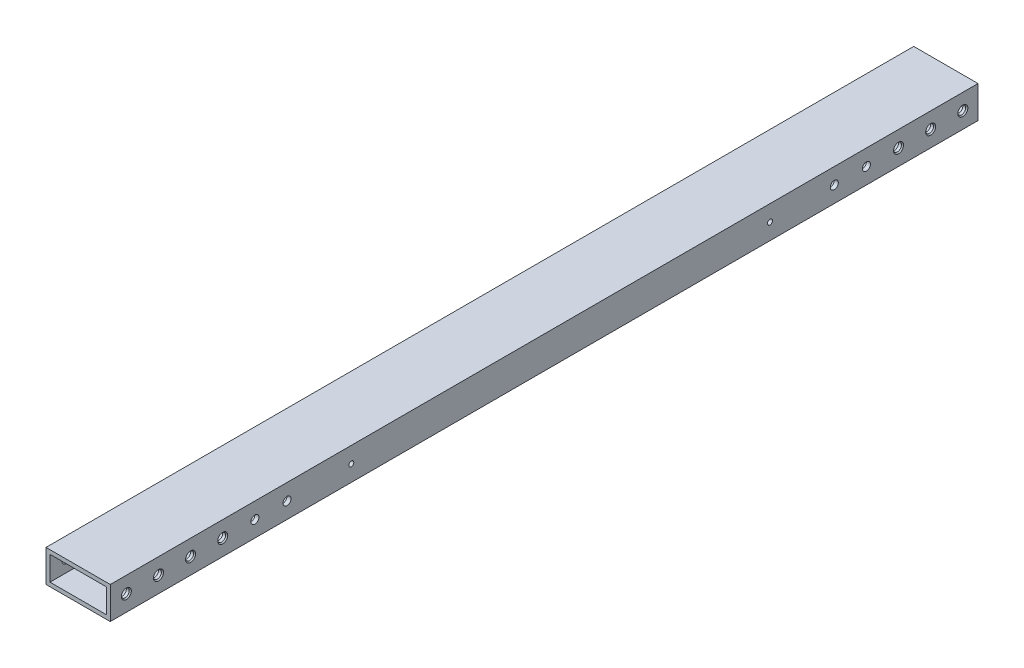
SolidWorks part; units mm, degrees
material "6061 Alloy"
ref_plane "Front Plane" through (0, 0, 0) normal (0, 0, 1) x (1, 0, 0)
ref_plane "Top Plane" through (0, 0, 0) normal (0, 1, 0) x (1, 0, 0)
ref_plane "Right Plane" through (0, 0, 0) normal (1, 0, 0) x (0, 0, -1)
sketch "Sketch1" plane through (0, 0, 0) normal (0, 0, 1) x (1, 0, 0)
  line L0 (-22.225, 9.525) -> (22.225, 9.525)
  line L2 (-25.4, 12.7) -> (25.4, 12.7)
  line L3 (-25.4, 12.7) -> (-25.4, -12.7)
  line L4 (-25.4, -12.7) -> (25.4, -12.7)
  line L5 (25.4, 12.7) -> (25.4, -12.7)
  line L10 (22.225, 9.525) -> (22.225, -9.525)
  line L11 (-22.225, -9.525) -> (22.225, -9.525)
  line L12 (-22.225, 9.525) -> (-22.225, -9.525)
  point P12 (0, 12.7)
  point P14 (25.4, 0)
  dimension "Wall Thickness" = 3.175
  dimension "Outside Width" = 50.8
  dimension "Outside Height" = 25.4
  dimension "Inside Height" = 19.05
  dimension "Inside Width" = 44.45
sketch "Sketch2" plane through (0, 0, 0) normal (1, 0, 0) x (0, 0, -1)
  line L0 (342.9, 0) -> (-342.9, 0)
  point P4 (0, 0)
  point P7 (-342.9, 0)
  point P10 (342.9, 0)
  dimension "Length" = 685.8
sketch "Sketch3" plane through (0, 0, 0) normal (0, 0, 1) x (1, 0, 0)
  line L21 (25.4, 12.7) -> (-25.4, 12.7)
  line L22 (25.4, -12.7) -> (25.4, 12.7)
  line L23 (-25.4, -12.7) -> (25.4, -12.7)
  line L24 (-25.4, 12.7) -> (-25.4, -12.7)
  line L25 (25.4, 12.7) -> (-25.4, 12.7)
  line L26 (25.4, -12.7) -> (25.4, 12.7)
  line L27 (-25.4, -12.7) -> (25.4, -12.7)
  line L28 (-25.4, 12.7) -> (-25.4, -12.7)
  line L29 (22.225, 9.525) -> (-22.225, 9.525)
  line L30 (22.225, -9.525) -> (22.225, 9.525)
  line L31 (-22.225, -9.525) -> (22.225, -9.525)
  line L32 (-22.225, 9.525) -> (-22.225, -9.525)
  line L33 (22.225, 9.525) -> (-22.225, 9.525)
  line L34 (22.225, -9.525) -> (22.225, 9.525)
  line L35 (-22.225, -9.525) -> (22.225, -9.525)
  line L36 (-22.225, 9.525) -> (-22.225, -9.525)
  dimension "D1" = 0
  dimension "D2" = 0
extrude "Boss-Extrude1" add sketch "Sketch3" along normal up to vertex (342.9 mm away) and the other way up to vertex (342.9 mm away) up to point (0, 0, 342.9) other way up to point (0, 0, -342.9)
sketch "Drawing Reference" plane through (0, 0, 0) normal (1, 0, 0) x (0, 0, -1)
  line L0 (-342.9, 0) -> (342.9, 0) construction
  line L1 (0, -12.7) -> (0, 12.7) construction
  line L2 (-342.9, -12.7) -> (342.9, -12.7) construction
  line L5 (-342.9, 12.7) -> (342.9, 12.7) construction
  point P7 (-306.324, 0)
  point P8 (306.324, 0)
  dimension "D1" = 36.576
sketch "Sketch5" plane through (25.4, 0, 0) normal (1, 0, 0) x (0, 0, -1)
  line L0 (-342.9, 0) -> (-279.4, 0)
  line L1 (-342.9, -12.7) -> (-342.9, 12.7) construction
  line L2 (-279.4, 0) -> (-254, 0)
  line L3 (-254, 0) -> (-228.6, 0)
  line L4 (-228.6, 0) -> (-203.2, 0)
sketch "Sketch8" plane through (25.4, 0, 0) normal (1, 0, 0) x (0, 0, -1)
  line L0 (342.9, 0) -> (305.5118, 0)
  line L1 (342.9, -12.7) -> (342.9, 12.7) construction
  line L2 (305.5118, 0) -> (280.1118, 0)
  line L3 (280.1118, 0) -> (254.7118, 0)
  line L4 (254.7118, 0) -> (229.3118, 0)
hole_wizard "1/4 (0.25) Diameter Hole3" positions "Sketch12" profile "Sketch13" hole size "1/4" standard "ANSI Inch" end condition through all
sketch "Sketch12" plane through (-25.4, 0, 0) normal (-1, 0, 0) x (0, 0, 1)
  point P0 (-330.9118, 0)
sketch "Sketch13" plane through (-25.4, 0, -330.9118) normal (0, 1, 0) x (0, 0, 1)
  line L0 (0, 0) -> (0, 50.8)
  line L1 (0, 50.8) -> (3.9624, 50.8)
  line L2 (3.175, 49.8942) -> (3.175, 0)
  line L5 (3.175, 0) -> (0, 0)
  line L7 (3.9624, 50.8) -> (3.175, 49.8942)
  line L8 (-3.9624, 50.8) -> (-3.175, 49.8942) construction
  line L11 (0, -6.35) -> (0, 107.95) construction
  dimension "Thru Hole Dia." = 6.35
  dimension "Thru Hole Depth" = 50.8
  dimension "Far C'Sink Dia." = 7.9248
  dimension "Far C'Sink Angle" = 82
hole_wizard "1/4 (0.25) Diameter Hole4" positions "Sketch14" profile "Sketch15" hole size "1/4" standard "ANSI Inch" end condition through all
sketch "Sketch14" plane through (-25.4, 0, 0) normal (-1, 0, 0) x (0, 0, 1)
  point P0 (304.8, 0)
  point P3 (330.2, 0)
sketch "Sketch15" plane through (-25.4, 0, 304.8) normal (0, 1, 0) x (0, 0, 1)
  line L0 (0, 0) -> (0, 50.8)
  line L1 (0, 50.8) -> (3.9624, 50.8)
  line L2 (3.175, 49.8942) -> (3.175, 0)
  line L5 (3.175, 0) -> (0, 0)
  line L7 (3.9624, 50.8) -> (3.175, 49.8942)
  line L8 (-3.9624, 50.8) -> (-3.175, 49.8942) construction
  line L11 (0, -6.35) -> (0, 107.95) construction
  dimension "Thru Hole Dia." = 6.35
  dimension "Thru Hole Depth" = 50.8
  dimension "Far C'Sink Dia." = 7.9248
  dimension "Far C'Sink Angle" = 82
hole_wizard "1/4 (0.25) Diameter Hole5" positions "Sketch17" profile "Sketch18" hole size "1/4" standard "ANSI Inch" end condition through all
sketch "Sketch17" plane through (25.4, 0, 0) normal (1, 0, 0) x (0, 0, -1)
  point P0 (305.5118, 0)
  point P3 (280.1118, 0)
sketch "Sketch18" plane through (25.4, 0, -305.5118) normal (0, 1, 0) x (0, 0, -1)
  line L0 (0, 0) -> (0, 50.8)
  line L1 (0, 50.8) -> (3.175, 50.8)
  line L2 (3.175, 50.8) -> (3.175, 0.9058)
  line L3 (3.175, 0.9058) -> (3.9624, 0)
  line L5 (3.9624, 0) -> (0, 0)
  line L6 (-3.175, 0.9058) -> (-3.9624, 0) construction
  line L11 (0, -6.35) -> (0, 107.95) construction
  dimension "Thru Hole Dia." = 6.35
  dimension "Thru Hole Depth" = 50.8
  dimension "Near C'Sink Dia." = 7.9248
  dimension "Near C'Sink Angle" = 82
hole_wizard "1/4 (0.25) Diameter Hole6" positions "Sketch19" profile "Sketch20" hole size "1/4" standard "ANSI Inch" end condition through all
sketch "Sketch19" plane through (25.4, 0, 0) normal (1, 0, 0) x (0, 0, -1)
  point P0 (229.3118, 0)
  point P3 (254.7118, 0)
sketch "Sketch20" plane through (25.4, 0, -229.3118) normal (0, 1, 0) x (0, 0, -1)
  line L0 (0, 0) -> (0, 50.8)
  line L1 (0, 50.8) -> (3.175, 50.8)
  line L2 (3.175, 50.8) -> (3.175, 0)
  line L5 (3.175, 0) -> (0, 0)
  line L11 (0, -6.35) -> (0, 107.95) construction
  dimension "Thru Hole Dia." = 6.35
  dimension "Thru Hole Depth" = 50.8
hole_wizard "1/4 (0.25) Diameter Hole7" positions "Sketch21" profile "Sketch22" hole size "1/4" standard "ANSI Inch" end condition through all
sketch "Sketch21" plane through (25.4, 0, 0) normal (1, 0, 0) x (0, 0, -1)
  point P0 (-203.2, 0)
  point P3 (-228.6, 0)
sketch "Sketch22" plane through (25.4, 0, 203.2) normal (0, 1, 0) x (0, 0, -1)
  line L0 (0, 0) -> (0, 50.8)
  line L1 (0, 50.8) -> (3.175, 50.8)
  line L2 (3.175, 50.8) -> (3.175, 0)
  line L5 (3.175, 0) -> (0, 0)
  line L11 (0, -6.35) -> (0, 107.95) construction
  dimension "Thru Hole Dia." = 6.35
  dimension "Thru Hole Depth" = 50.8
hole_wizard "1/4 (0.25) Diameter Hole8" positions "Sketch23" profile "Sketch24" hole size "1/4" standard "ANSI Inch" end condition through all
sketch "Sketch23" plane through (25.4, 0, 0) normal (1, 0, 0) x (0, 0, -1)
  point P0 (-279.4, 0)
  point P3 (-254, 0)
sketch "Sketch24" plane through (25.4, 0, 279.4) normal (0, 1, 0) x (0, 0, -1)
  line L0 (0, 0) -> (0, 50.8)
  line L1 (0, 50.8) -> (3.175, 50.8)
  line L2 (3.175, 50.8) -> (3.175, 0.9058)
  line L3 (3.175, 0.9058) -> (3.9624, 0)
  line L5 (3.9624, 0) -> (0, 0)
  line L6 (-3.175, 0.9058) -> (-3.9624, 0) construction
  line L11 (0, -6.35) -> (0, 107.95) construction
  dimension "Thru Hole Dia." = 6.35
  dimension "Thru Hole Depth" = 50.8
  dimension "Near C'Sink Dia." = 7.9248
  dimension "Near C'Sink Angle" = 82
sketch "Sketch25" plane through (25.4, 0, 0) normal (1, 0, 0) x (0, 0, -1)
  line L0 (-203.2, 0) -> (-152.4, 0)
  line L1 (229.3118, 0) -> (178.5118, 0)
hole_wizard "5/32 (0.15625) Diameter Hole1" positions "Sketch26" profile "Sketch27" hole size "5/32" standard "ANSI Inch" end condition through all
sketch "Sketch26" plane through (25.4, 0, 0) normal (1, 0, 0) x (0, 0, -1)
  point P0 (-152.4, 0)
  point P3 (178.5118, 0)
sketch "Sketch27" plane through (25.4, 0, 152.4) normal (0, 1, 0) x (0, 0, -1)
  line L0 (0, 0) -> (0, 50.8)
  line L1 (0, 50.8) -> (1.9844, 50.8)
  line L2 (1.9844, 50.8) -> (1.9844, 0)
  line L5 (1.9844, 0) -> (0, 0)
  line L11 (0, -6.35) -> (0, 107.95) construction
  dimension "Thru Hole Dia." = 3.9688
  dimension "Thru Hole Depth" = 50.8
sketch "Sketch30" plane through (-25.4, 0, 0) normal (-1, 0, 0) x (0, 0, 1)
  line L0 (203.2, 0) -> (184.15, 0)
  line L1 (203.2, 0) -> (152.4, 0) construction
  point P0 (-210.2618, 0)
hole_wizard "1/2 (0.5) Diameter Hole1" positions "Sketch33" profile "Sketch34" hole size "1/2" standard "ANSI Inch"
sketch "Sketch33" plane through (-25.4, 0, 0) normal (-1, 0, 0) x (0, 0, 1)
  point P0 (-210.2618, 0)
  point P3 (184.15, 0)
sketch "Sketch34" plane through (-25.4, 0, -210.2618) normal (0, 1, 0) x (0, 0, 1)
  line L0 (0, 0) -> (0, 10.1655)
  line L1 (0, 10.1655) -> (6.35, 6.35)
  line L2 (6.35, 6.35) -> (6.35, 0)
  line L5 (6.35, 0) -> (0, 0)
  line L10 (0, 10.1655) -> (-6.35, 6.35) construction
  line L11 (0, -6.35) -> (0, 107.95) construction
  dimension "Hole Dia." = 12.7
  dimension "Hole Depth" = 6.35
  dimension "Drill Angle" = 118
equation "\"D1@Drawing Reference\"=\"Outside Width@Sketch1\" * 0.72"
